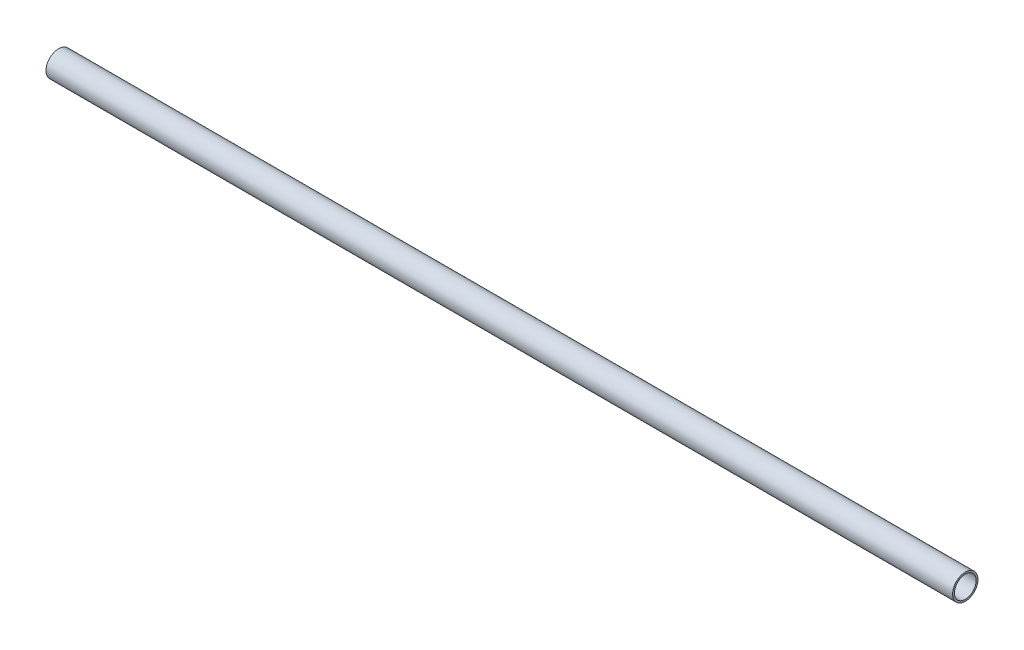
SolidWorks part; units mm, degrees
material "Thornel Mat VMA"
ref_plane "Ön Düzlem" through (0, 0, 0) normal (0, 0, 1) x (1, 0, 0)
ref_plane "Üst Düzlem" through (0, 0, 0) normal (0, 1, 0) x (1, 0, 0)
ref_plane "Sağ Düzlem" through (0, 0, 0) normal (1, 0, 0) x (0, 0, -1)
sketch "Çizim1" plane through (0, 0, 0) normal (1, 0, 0) x (0, 0, -1)
  circle A0 centre (0, 0) radius 7
  circle A1 centre (0, 0) radius 6
  dimension "D1" = 14
  dimension "D2" = 12
extrude "Yükseklik-Ekstrüzyon1" add sketch "Çizim1" along normal mid plane 500
sketch "Çizim2" plane through (250, 0, 0) normal (1, 0, 0) x (0, 0, -1)
  line L0 (0, -7) -> (0, 7) construction
  circle A0 centre (0, 0) radius 7 construction
  point P7 (0, 0)
